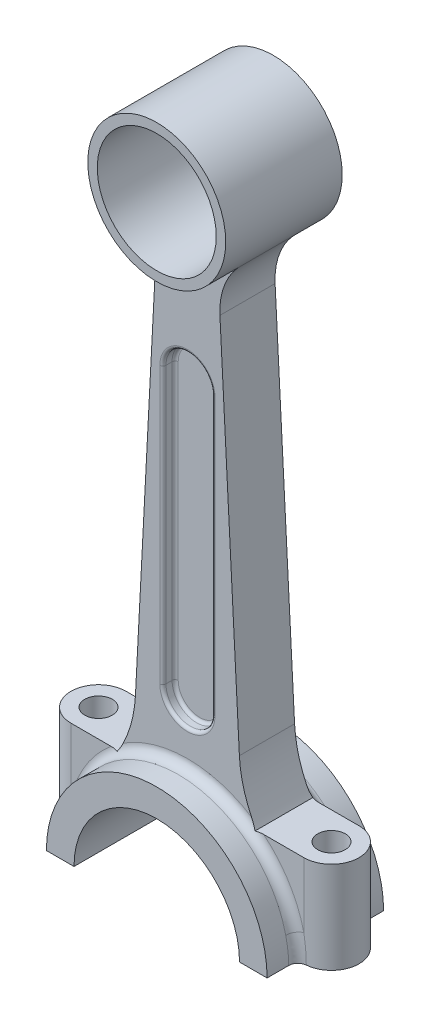
SolidWorks part; units mm, degrees
ref_plane "Front Plane" through (0, 0, 0) normal (0, 0, 1) x (1, 0, 0)
ref_plane "Top Plane" through (0, 0, 0) normal (0, 1, 0) x (1, 0, 0)
ref_plane "Right Plane" through (0, 0, 0) normal (1, 0, 0) x (0, 0, -1)
sketch "Sketch1" plane through (0, 0, 0) normal (0, 0, 1) x (1, 0, 0)
  line L0 (0, 0) -> (0, -201.2) construction
  line L1 (-10, -20.1556) -> (-17.8497, -169.9368)
  line L2 (10, -20.1556) -> (17.8497, -169.9368)
  line L3 (-36, -201.2) -> (-27, -201.2)
  line L4 (27, -201.2) -> (36, -201.2)
  circle A0 centre (0, 0) radius 22.5
  circle A1 centre (0, 0) radius 19.4
  arc A2 (27, -201.2) -> (-27, -201.2) centre (0, -201.2) ccw
  arc A3 (36, -201.2) -> (-36, -201.2) centre (0, -201.2) ccw
  dimension "D1" = 45
  dimension "D2" = 38.8
  dimension "D3" = 72
  dimension "D4" = 54
  dimension "D5" = 201.2
  dimension "D6" = 6
  dimension "D7" = 20
extrude "Boss-Extrude1" add sketch "Sketch1" along normal mid plane 38 contours A0 | A1 | A3 L3 A2 L4
extrude "Boss-Extrude2" add sketch "Sketch1<3>" along normal mid plane 18 contours L0 A0 L1 A3 | A0 L0 A3 L2 region at (7.1843, -100.8455, 0) region at (-7.1843, -100.8455, 0)
sketch "Sketch1<3>" plane through (0, 0, 0) normal (0, 0, 1) x (1, 0, 0) same geometry as "Sketch1"
sketch "Sketch3" plane through (0, 0, 9) normal (0, 0, 1) x (1, 0, 0)
  line L0 (0, 0) -> (0, -201.2) construction
  line L1 (0, -55.6) -> (0, -145.6) construction
  line L2 (8, -55.6) -> (8, -145.6)
  line L3 (-8, -55.6) -> (-8, -145.6)
  arc A0 (8, -55.6) -> (-8, -55.6) centre (0, -55.6) ccw
  arc A1 (-8, -145.6) -> (8, -145.6) centre (0, -145.6) ccw
  point P6 (0, -100.6)
  dimension "D2" = 8
  dimension "D1" = 90
extrude "Cut-Extrude1" cut sketch "Sketch3" against normal blind 4
mirror "Mirror1" about plane through (0, 0, 0) normal (0, 0, 1) of "Cut-Extrude1"
fillet "Fillet1" radius 1 16 edges at (8, -100.6, -9) (0, -153.6, -9) (-8, -100.6, -9) (0, -47.6, 9) (8, -100.6, 9) (0, -153.6, 9) (0, -47.6, -9) (-8, -100.6, 9) (8, -100.6, 5) (0, -153.6, 5) (-8, -100.6, 5) (0, -47.6, 5) (-8, -100.6, -5) (0, -153.6, -5) (8, -100.6, -5) (0, -47.6, -5)
fillet "Fillet2" radius 40 2 edges at (17.8497, -169.9368, 0) (-17.8497, -169.9368, 0)
fillet "Fillet3" radius 22.5 2 edges at (-10, -20.1556, 0) (10, -20.1556, 0)
ref_plane "Plane1" through (0, -171.2, 0) normal (0, -1, 0) x (-1, 0, 0)
sketch "Sketch4" plane through (0, -171.2, 0) normal (0, -1, 0) x (-1, 0, 0)
  line L0 (38, 0) -> (-38, 0) construction
  line L1 (36, -19) -> (36, 19) construction
  line L2 (36, 0) -> (-36.4862, 0) construction
  line L3 (38, -9) -> (-38, -9)
  line L4 (38, 9) -> (-38, 9)
  arc A0 (38, -9) -> (38, 9) centre (38, 0) ccw
  arc A1 (-38, 9) -> (-38, -9) centre (-38, 0) ccw
  point P7 (0, 0)
  dimension "D2" = 9
  dimension "D1" = 76
extrude "Boss-Extrude3" add sketch "Sketch4" along normal up to surface (30 mm away) up to face at (31.5, -201.2, 0)
sketch "Sketch6" plane through (0, 0, -9) normal (0, 0, -1) x (-1, 0, 0)
  line L1 (-27, -201.2) -> (27, -201.2)
  line L2 (-27, -201.2) -> (27, -201.2)
  arc A1 (27, -201.2) -> (-27, -201.2) centre (0, -201.2) ccw
  arc A2 (27, -201.2) -> (-27, -201.2) centre (0, -201.2) ccw
  dimension "D1" = 0
extrude "Cut-Extrude2" cut sketch "Sketch6" against normal through all
sketch "Sketch7" plane through (0, -171.2, 0) normal (0, -1, 0) x (-1, 0, 0)
  circle A0 centre (38, 0) radius 4.5
  circle A1 centre (-38, 0) radius 4.5
  point P4 (0, 0)
  point P9 (0, 0)
  dimension "D1" = 9
  dimension "D2" = 9
extrude "Cut-Extrude3" cut sketch "Sketch7" along normal through all
fillet "Fillet4" radius 3 2 edges at (0, -165.2, -9) (0, -165.2, 9)
